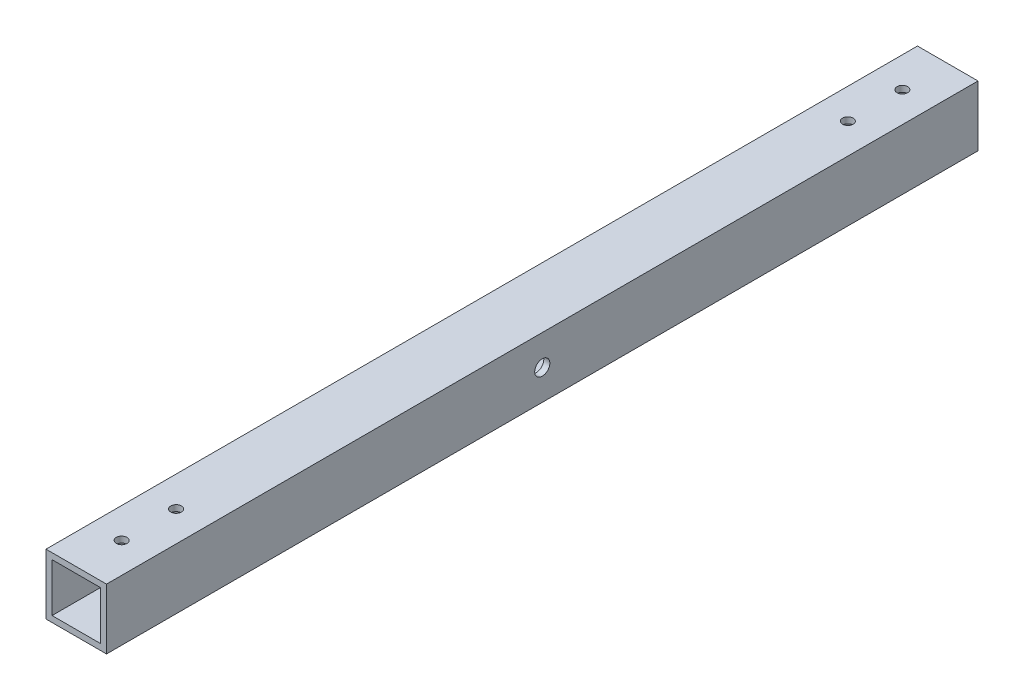
SolidWorks part; units mm, degrees
ref_plane "Front Plane" through (0, 0, 0) normal (0, 0, 1) x (1, 0, 0)
ref_plane "Top Plane" through (0, 0, 0) normal (0, 1, 0) x (1, 0, 0)
ref_plane "Right Plane" through (0, 0, 0) normal (1, 0, 0) x (0, 0, -1)
sketch "Sketch1" plane through (0, 0, 0) normal (0, 0, 1) x (1, 0, 0)
  line L0 (31.75, 0) -> (25.4, 0) construction
  line L1 (-31.75, 0) -> (31.75, 0) construction
  line L2 (0, 31.75) -> (0, -31.75)
  point P7 (0, 0)
sketch "Sketch2" plane through (0, 0, 0) normal (1, 0, 0) x (0, 0, -1)
  line L0 (457.2, 0) -> (-457.2, 0)
  point P4 (0, 0)
  dimension "Length" = 914.4
sketch "Sketch3" plane through (0, 0, 0) normal (0, 0, 1) x (1, 0, 0)
  line L0 (-31.75, 0) -> (31.75, 0) construction
  line L5 (31.75, -31.75) -> (-31.75, -31.75)
  line L6 (31.75, -31.75) -> (31.75, 31.75)
  line L11 (31.75, 31.75) -> (-31.75, 31.75)
  line L12 (-31.75, -31.75) -> (-31.75, 31.75)
  line L14 (31.75, -31.75) -> (-31.75, 31.75) construction
  line L15 (31.75, 31.75) -> (-31.75, -31.75) construction
  line L16 (25.4, -25.4) -> (-25.4, -25.4)
  line L17 (25.4, -25.4) -> (25.4, 25.4)
  line L18 (25.4, 25.4) -> (-25.4, 25.4)
  line L19 (-25.4, -25.4) -> (-25.4, 25.4)
  line L20 (25.4, -25.4) -> (-25.4, 25.4) construction
  line L21 (25.4, 25.4) -> (-25.4, -25.4) construction
  point P0 (0, 0)
  point P5 (0, 0)
  point P13 (25.4, -31.75)
  dimension "D1" = 6.35
  dimension "D3" = 63.5
  dimension "D4" = 63.5
  dimension "D2" = 6.35
extrude "Boss-Extrude1" add sketch "Sketch3" along normal up to vertex (457.2 mm away) and the other way up to vertex (457.2 mm away) up to point (0, 0, 457.2) other way up to point (0, 0, -457.2)
sketch "Sketch5" plane through (0, 0, 0) normal (1, 0, 0) x (0, 0, -1)
  line L0 (-457.2, 0) -> (457.2, 0) construction
  line L3 (-457.2, -31.75) -> (-457.2, 31.75) construction
  line L4 (457.2, -31.75) -> (457.2, 31.75) construction
  point P6 (-385.7625, 0)
  point P7 (-361.95, 0)
  point P8 (361.95, 0)
  point P10 (385.7625, 0)
  dimension "D1" = 71.4375
  dimension "D2" = 95.25
  dimension "D3" = 71.4375
  dimension "D4" = 95.25
sketch "Sketch6" plane through (0, 31.75, 0) normal (0, 1, 0) x (1, 0, 0)
  line L0 (0, 457.2) -> (0, 388.9644) construction
  line L1 (31.75, 457.2) -> (-31.75, 457.2) construction
  line L2 (31.75, -457.2) -> (-31.75, -457.2) construction
  line L3 (0, -457.2) -> (0, -352.425) construction
  circle A0 centre (0, 409.575) radius 5.588
  circle A1 centre (0, -409.575) radius 5.588
  circle A2 centre (0, -352.425) radius 5.588
  circle A3 centre (0, 352.425) radius 5.588
  dimension "D5" = 11.176
  dimension "D6" = 11.176
  dimension "D7" = 11.176
  dimension "D8" = 11.176
  dimension "D1" = 47.625
  dimension "D2" = 47.625
  dimension "D3" = 57.15
  dimension "D4" = 57.15
extrude "Cut-Extrude1" cut sketch "Sketch6" against normal through all
sketch "Sketch7" plane through (31.75, 0, 0) normal (1, 0, 0) x (0, 0, -1)
  line L1 (-457.2, -31.75) -> (457.2, -31.75) construction
  line L2 (-457.2, -31.75) -> (-457.2, 31.75) construction
  line L3 (-457.2, 31.75) -> (457.2, 31.75) construction
  line L4 (457.2, -31.75) -> (457.2, 31.75) construction
  line L5 (-457.2, -31.75) -> (457.2, 31.75) construction
  line L6 (-457.2, 31.75) -> (457.2, -31.75) construction
  circle A0 centre (0, 0) radius 7.9375
  point P0 (0, 0)
  dimension "D1" = 15.875
extrude "Cut-Extrude2" cut sketch "Sketch7" against normal through all
sketch "Sketch9" plane through (0, 31.75, 0) normal (0, 1, 0) x (1, 0, 0)
  line L0 (0, 0) -> (0, 203.2)
  point P5 (0, 203.2)
  dimension "D1" = 203.2
equation "\"D1@Sketch3\"=\"Wall thickness@Sketch1\""
equation "\"D1@Sketch5\"=\"Width@Sketch1\"*1.125"
equation "\"D2@Sketch5\"=\"Width@Sketch1\"*1.5"
equation "\"D3@Sketch5\"=\"D1@Sketch5\""
equation "\"D4@Sketch5\"=\"D2@Sketch5\""
equation "\"D2@Sketch3\"=\"Wall Thickness@Sketch1\""
